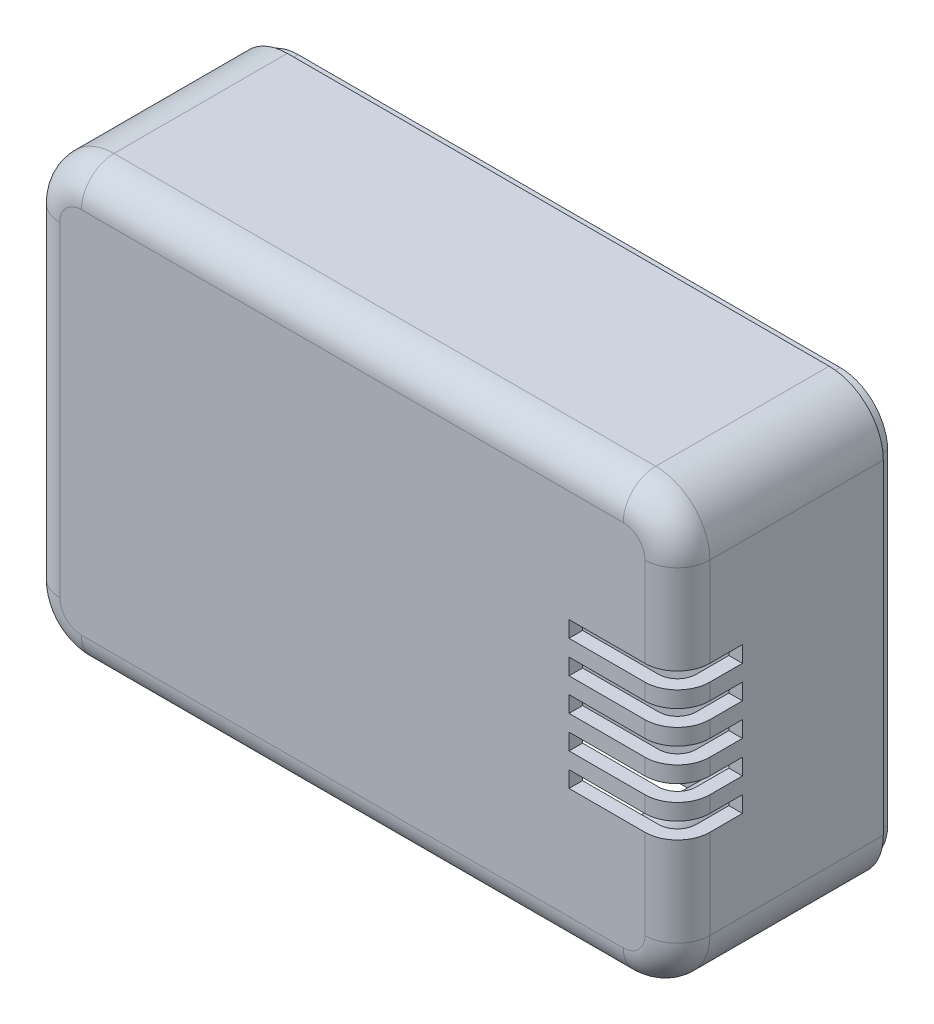
SolidWorks part; units mm, degrees
ref_plane "前视基准面" through (0, 0, 0) normal (0, 0, 1) x (1, 0, 0)
ref_plane "上视基准面" through (0, 0, 0) normal (0, 1, 0) x (1, 0, 0)
ref_plane "右视基准面" through (0, 0, 0) normal (1, 0, 0) x (0, 0, -1)
sketch "草图1" plane through (0, 0, 0) normal (0, 0, 1) x (1, 0, 0)
  line L0 (-50, -40) -> (50, -40)
  line L1 (60, -30) -> (60, 30)
  line L2 (50, 40) -> (-50, 40)
  line L3 (-60, 30) -> (-60, -30)
  arc A0 (-60, -30) -> (-50, -40) centre (-50, -30) ccw
  arc A1 (50, -40) -> (60, -30) centre (50, -30) ccw
  arc A2 (60, 30) -> (50, 40) centre (50, 30) ccw
  arc A3 (-50, 40) -> (-60, 30) centre (-50, 30) ccw
extrude "凸台-拉伸1" add sketch "草图1" along normal blind 40
fillet "圆角1" radius 6 8 edges at (-57.0711, -37.0711, 40) (-57.0711, 37.0711, 40) (57.0711, -37.0711, 40) (57.0711, 37.0711, 40) (60, 0, 40) (-60, 0, 40) (0, 40, 40) (0, -40, 40)
shell "抽壳1" thickness 2.5 removed face at (0, -40, 17)
sketch "草图2" plane through (0, 0, 0) normal (0, 0, 1) x (1, 0, 0)
  line L0 (-50, -40) -> (50, -40)
  line L1 (60, -30) -> (60, 30)
  line L2 (50, 40) -> (-50, 40)
  line L3 (-60, 30) -> (-60, -30)
  line L4 (-50, -38.8) -> (50, -38.8)
  line L5 (58.8, -30) -> (58.8, 30)
  line L6 (50, 38.8) -> (-50, 38.8)
  line L7 (-58.8, 30) -> (-58.8, -30)
  arc A0 (-60, -30) -> (-50, -40) centre (-50, -30) ccw
  arc A1 (50, -40) -> (60, -30) centre (50, -30) ccw
  arc A2 (60, 30) -> (50, 40) centre (50, 30) ccw
  arc A3 (-50, 40) -> (-60, 30) centre (-50, 30) ccw
  arc A4 (-58.8, -30) -> (-50, -38.8) centre (-50, -30) ccw
  arc A5 (50, -38.8) -> (58.8, -30) centre (50, -30) ccw
  arc A6 (58.8, 30) -> (50, 38.8) centre (50, 30) ccw
  arc A7 (-50, 38.8) -> (-58.8, 30) centre (-50, 30) ccw
extrude "切除-拉伸1" cut sketch "草图2" along normal blind 2
ref_plane "基准面1" through (0, -13.5, 0) normal (0, 1, 0) x (1, 0, 0)
sketch "草图3" plane through (0, -13.5, 0) normal (0, 1, 0) x (1, 0, 0)
  line L0 (40, -28) -> (61, -28)
  line L1 (61, -28) -> (61, -41)
  line L2 (61, -41) -> (40, -41)
  line L3 (40, -41) -> (40, -28)
extrude "切除-拉伸2" cut sketch "草图3" along normal blind 3
pattern_linear "阵列(线性)1" count 5 spacing 6 along (0, 1, 0) of "切除-拉伸2"
ref_plane "基准面2" through (0, 0, 37.5) normal (0, 0, 1) x (1, 0, 0)
sketch "草图4" plane through (0, 0, 37.5) normal (0, 0, 1) x (1, 0, 0)
  circle A0 centre (45, 25) radius 4
  circle A1 centre (45, -25) radius 4
  circle A2 centre (-45, 25) radius 4
  circle A3 centre (-45, -25) radius 4
extrude "凸台-拉伸2" add sketch "草图4" against normal blind 32.5
ref_plane "基准面3" through (0, 0, 5) normal (0, 0, 1) x (1, 0, 0)
sketch "草图5" plane through (0, 0, 5) normal (0, 0, 1) x (1, 0, 0)
  circle A0 centre (45, 25) radius 1.25
  circle A1 centre (45, -25) radius 1.25
  circle A2 centre (-45, 25) radius 1.25
  circle A3 centre (-45, -25) radius 1.25
extrude "切除-拉伸3" cut sketch "草图5" along normal blind 12
